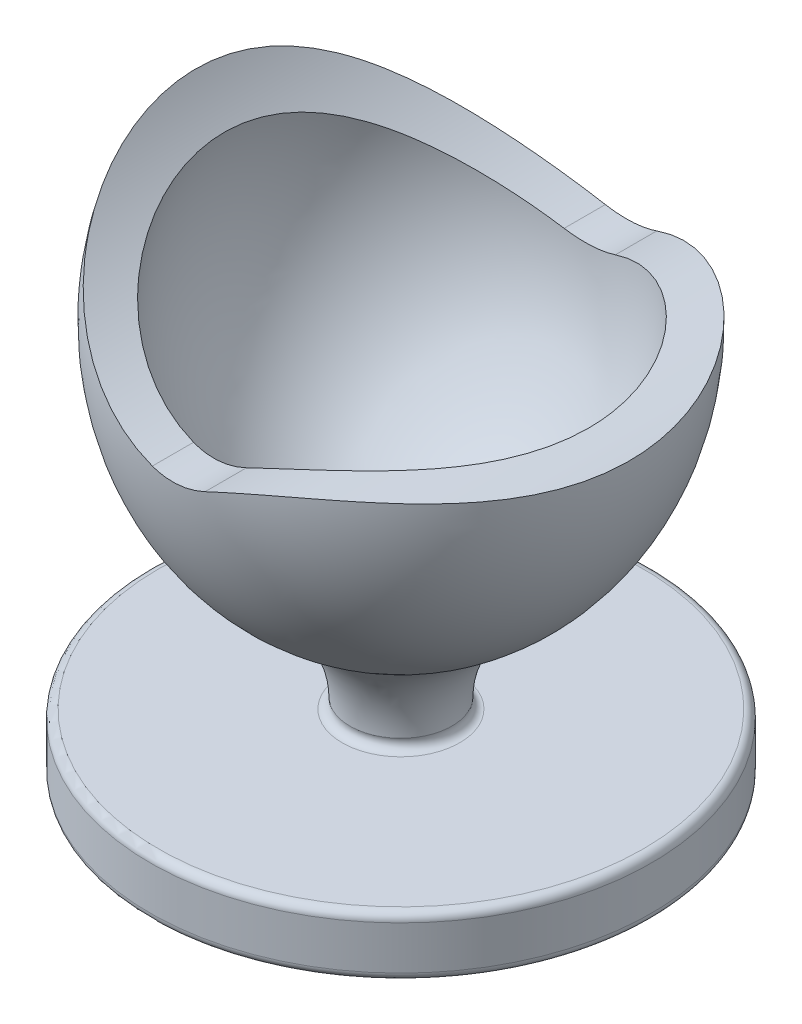
SolidWorks part; units mm, degrees
ref_plane "Ön Düzlem" through (0, 0, 0) normal (0, 0, 1) x (1, 0, 0)
ref_plane "Üst Düzlem" through (0, 0, 0) normal (0, 1, 0) x (1, 0, 0)
ref_plane "Sağ Düzlem" through (0, 0, 0) normal (1, 0, 0) x (0, 0, -1)
sketch "Çizim1" plane through (0, 0, 0) normal (0, 0, 1) x (1, 0, 0)
  line L0 (0, 32) -> (0, -32)
  ellipse E0 centre (0, 0) end of major axis (0, 32) minor radius 28 (0, -32) -> (0, 32) ccw
  dimension "D1" = 28
  dimension "D2" = 32
revolve "Döndür1" add sketch "Çizim1" angle 360 about L0
sketch "Çizim2" plane through (0, 0, 0) normal (0, 0, 1) x (1, 0, 0)
  line L0 (35.9089, -4.0497) -> (26.0891, 34.307)
  line L1 (26.0891, 34.307) -> (-3.0819, 40.4188)
  line L2 (-3.0819, 40.4188) -> (-28.9486, 23.6334)
  arc A0 (35.9089, -4.0497) -> (3.6772, -2.505) centre (18.1581, -37.3928) ccw
  arc A1 (-2.706, -2.9386) -> (-28.9486, 23.6334) centre (6.6502, 32.5463) cw
  arc A2 (-2.706, -2.9386) -> (3.6772, -2.505) centre (-0.1564, 6.731) ccw
  dimension "D1" = 10
extrude "Kes-Ekstrüzyon1" cut sketch "Çizim2" against normal through all and the other way through all
shell "İç Boşaltma1" thickness 5 removed face at (-13.9077, 5.6109, -0.0202) removed face at (0.5029, -2.984, 0.0001) removed face at (15.8186, -1.709, 0.633)
sketch "Çizim3" plane through (0, 0, 0) normal (0, 0, 1) x (1, 0, 0)
  line L0 (0, -32) -> (0, -41.6295)
  line L1 (-7.1978, -41.2269) -> (-29.7069, -41.2269)
  line L2 (-30.7069, -42.2269) -> (-30.7069, -47.5503)
  line L3 (-29.7069, -48.5503) -> (0, -48.5503)
  line L4 (0, -48.5503) -> (0, -41.6295)
  arc A0 (-12.0571, -28.8812) -> (-6.2449, -39.9237) centre (-19.6256, -39.9158) cw
  arc A1 (-30.7069, -47.5503) -> (-29.7069, -48.5503) centre (-29.7069, -47.5503) ccw
  arc A2 (-30.7069, -42.2269) -> (-29.7069, -41.2269) centre (-29.7069, -42.2269) cw
  arc A3 (-6.2449, -39.9237) -> (-7.1978, -41.2269) centre (-7.1978, -40.2269) cw
  ellipse E0 centre (0, 0) end of major axis (0, 32) minor radius 28 (-25.1094, 14.1603) -> (0, -32) ccw construction
  ellipse E1 centre (0, 0) end of major axis (0, 32) minor radius 28 (-12.0571, -28.8812) -> (0, -32) ccw
  dimension "D1" = 1
revolve "Döndür2" add sketch "Çizim3" angle 360 about L0
